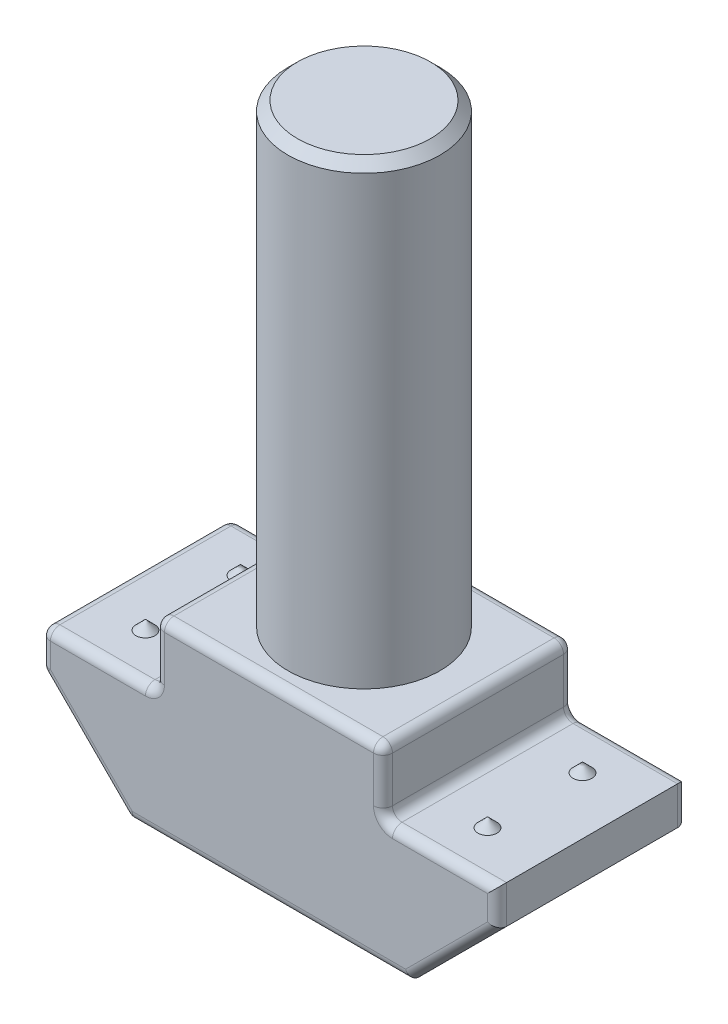
SolidWorks part; units mm, degrees
material "Acciaio inossidabile al cromo"
ref_plane "Piano frontale" through (0, 0, 0) normal (0, 0, 1) x (1, 0, 0)
ref_plane "Piano superiore" through (0, 0, 0) normal (0, 1, 0) x (1, 0, 0)
ref_plane "Piano destro" through (0, 0, 0) normal (1, 0, 0) x (0, 0, -1)
sketch "Schizzo1" plane through (0, 0, 0) normal (0, 0, 1) x (1, 0, 0)
  line L10 (3.7, 0) -> (-3.7, 0)
  line L11 (-3.7, 0) -> (-6, 2.3)
  line L12 (-6, 2.3) -> (-6, 3.3)
  line L13 (-6, 3.3) -> (-3, 3.3)
  line L14 (-3, 3.3) -> (-3, 5)
  line L15 (-3, 5) -> (3, 5)
  line L20 (0, 0) -> (0, 5) construction
  line L21 (0, -3.19) -> (0, 3.19) construction
  line L22 (6, 3.3) -> (3, 3.3)
  line L23 (6, 2.3) -> (6, 3.3)
  line L24 (3.7, 0) -> (6, 2.3)
  line L25 (3, 3.3) -> (3, 5)
  dimension "D1" = 3
  dimension "D2" = 3.3
  dimension "D3" = 1
  dimension "D4" = 45
  dimension "D5" = 6
  dimension "D6" = 5
extrude "Estrusione-Estrusione1" add sketch "Schizzo1" along normal blind 5
ref_plane "Piano1" through (0, 0, 2.5) normal (0, 0, 1) x (1, 0, 0)
fillet "Raccordo1" radius 0.25 27 edges at (3, 3.3, 2.5) (3, 5, 2.5) (-4.5, 3.3, 5) (0, 5, 5) (3, 4.15, 5) (4.5, 3.3, 5) (6, 2.8, 5) (4.85, 1.15, 5) (0, 0, 5) (-3, 5, 2.5) (-3, 4.15, 5) (-3, 3.3, 2.5) (-6, 3.3, 2.5) (-6, 2.8, 5) (-6, 2.3, 2.5) (-4.85, 1.15, 5) (-3.7, 0, 2.5) (0, 0, 0) (4.85, 1.15, 0) (6, 2.8, 0) (4.5, 3.3, 0) (3, 4.15, 0) (0, 5, 0) (-3, 4.15, 0) (-4.5, 3.3, 0) (-6, 2.8, 0) (-4.85, 1.15, 0)
sketch "Schizzo7" plane through (0, 5, 0) normal (0, 1, 0) x (1, 0, 0)
  line L0 (-2.75, -2.5) -> (2.75, -2.5) construction
  line L1 (-2.75, -0.25) -> (-2.75, -4.75) construction
  line L2 (2.75, -4.75) -> (2.75, -0.25) construction
  circle A0 centre (0, -2.5) radius 2
  dimension "D1" = 4
extrude "Estrusione-Estrusione3" add sketch "Schizzo7" along normal blind 12
cosmetic thread "Filettatura cosmetica1" parameters "D2"=3.22
chamfer "Smusso1" distance 0.25 angle 45 1 edges at (0, 17, 4.5)
ref_plane "Piano4" through (0, 0, 1.25) normal (0, 0, 1) x (1, 0, 0)
sketch "Schizzo8" plane through (0, 0, 1.25) normal (0, 0, 1) x (1, 0, 0)
  line L0 (-4.5, 3.3) -> (-4.5, 3.55)
  line L1 (-5.75, 3.3) -> (-3.25, 3.3) construction
  line L2 (-4.5, 3.55) -> (-4.75, 3.3)
  line L3 (-4.75, 3.3) -> (-4.5, 3.3)
  line L4 (-4.5, 3.3) -> (-4.5, 4.2152) construction
  dimension "D1" = 0.25
  dimension "D2" = 45
revolve "Rivoluzione2" add sketch "Schizzo8" angle 360 about L4
mirror "Specchia3" about plane through (0, 0, 0) normal (1, 0, 0) of "Rivoluzione2"
mirror "Specchia4" about plane through (0, 0, 2.5) normal (0, 0, 1) of "Specchia3"
